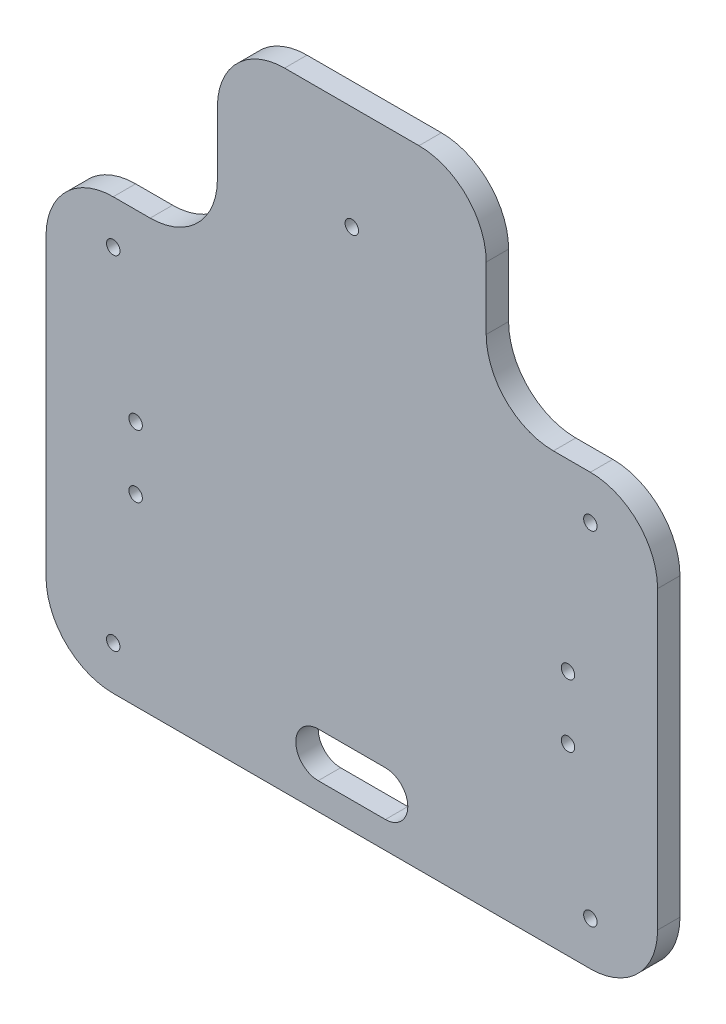
SolidWorks part; units mm, degrees
material "Acrylic (Medium-high impact)"
ref_plane "Front Plane" through (0, 0, 0) normal (0, 0, 1) x (1, 0, 0)
ref_plane "Top Plane" through (0, 0, 0) normal (0, 1, 0) x (1, 0, 0)
ref_plane "Right Plane" through (0, 0, 0) normal (1, 0, 0) x (0, 0, -1)
sketch "Model" plane through (0, 0, 0) normal (0, 0, 1) x (1, 0, 0)
  line L0 (836.1886, 1132.0702) -> (835.7887, 1132.0702)
  line L1 (836.1886, 1132.0702) -> (835.7887, 1132.0702)
  line L2 (836.5018, 1132.0643) -> (836.1886, 1132.0702)
  line L3 (836.5018, 1132.0643) -> (836.1886, 1132.0702)
  line L4 (836.7677, 1132.0446) -> (836.5018, 1132.0643)
  line L5 (836.7677, 1132.0446) -> (836.5018, 1132.0643)
  line L6 (836.9883, 1132.0111) -> (836.7677, 1132.0446)
  line L7 (836.9883, 1132.0111) -> (836.7677, 1132.0446)
  line L8 (837.1636, 1131.9638) -> (836.9883, 1132.0111)
  line L9 (837.1636, 1131.9638) -> (836.9883, 1132.0111)
  line L10 (837.3133, 1131.9008) -> (837.1636, 1131.9638)
  line L11 (837.3133, 1131.9008) -> (837.1636, 1131.9638)
  line L12 (837.4611, 1131.8141) -> (837.3133, 1131.9008)
  line L13 (837.4611, 1131.8141) -> (837.3133, 1131.9008)
  line L14 (837.6029, 1131.7077) -> (837.4611, 1131.8141)
  line L15 (837.6029, 1131.7077) -> (837.4611, 1131.8141)
  line L16 (837.7408, 1131.5777) -> (837.6029, 1131.7077)
  line L17 (837.7408, 1131.5777) -> (837.6029, 1131.7077)
  line L18 (837.8156, 1131.495) -> (837.7408, 1131.5777)
  line L19 (837.8156, 1131.495) -> (837.7408, 1131.5777)
  line L20 (837.9082, 1131.3847) -> (837.8156, 1131.495)
  line L21 (837.9082, 1131.3847) -> (837.8156, 1131.495)
  line L22 (838.0146, 1131.2468) -> (837.9082, 1131.3847)
  line L23 (838.0146, 1131.2468) -> (837.9082, 1131.3847)
  line L24 (838.1367, 1131.0833) -> (838.0146, 1131.2468)
  line L25 (838.1367, 1131.0833) -> (838.0146, 1131.2468)
  line L26 (838.2746, 1130.8903) -> (838.1367, 1131.0833)
  line L27 (838.2746, 1130.8903) -> (838.1367, 1131.0833)
  line L28 (838.4262, 1130.6716) -> (838.2746, 1130.8903)
  line L29 (838.4262, 1130.6716) -> (838.2746, 1130.8903)
  line L30 (838.5956, 1130.4254) -> (838.4262, 1130.6716)
  line L31 (838.5956, 1130.4254) -> (838.4262, 1130.6716)
  line L32 (838.7788, 1130.1516) -> (838.5956, 1130.4254)
  line L33 (838.7788, 1130.1516) -> (838.5956, 1130.4254)
  line L34 (840.1971, 1128.0361) -> (838.7788, 1130.1516)
  line L35 (840.1971, 1128.0361) -> (838.7788, 1130.1516)
  line L36 (842.5963, 1128.0361) -> (840.1971, 1128.0361)
  line L37 (842.5963, 1128.0361) -> (840.1971, 1128.0361)
  line L38 (841.4104, 1129.9369) -> (842.5963, 1128.0361)
  line L39 (841.4104, 1129.9369) -> (842.5963, 1128.0361)
  line L40 (841.2371, 1130.2127) -> (841.4104, 1129.9369)
  line L41 (841.2371, 1130.2127) -> (841.4104, 1129.9369)
  line L42 (841.0716, 1130.4648) -> (841.2371, 1130.2127)
  line L43 (841.0716, 1130.4648) -> (841.2371, 1130.2127)
  line L44 (840.916, 1130.6953) -> (841.0716, 1130.4648)
  line L45 (840.916, 1130.6953) -> (841.0716, 1130.4648)
  line L46 (840.7703, 1130.9041) -> (840.916, 1130.6953)
  line L47 (840.7703, 1130.9041) -> (840.916, 1130.6953)
  line L48 (840.6324, 1131.0892) -> (840.7703, 1130.9041)
  line L49 (840.6324, 1131.0892) -> (840.7703, 1130.9041)
  line L50 (840.5044, 1131.2527) -> (840.6324, 1131.0892)
  line L51 (840.5044, 1131.2527) -> (840.6324, 1131.0892)
  line L52 (840.3862, 1131.3945) -> (840.5044, 1131.2527)
  line L53 (840.3862, 1131.3945) -> (840.5044, 1131.2527)
  line L54 (840.2759, 1131.5147) -> (840.3862, 1131.3945)
  line L55 (840.2759, 1131.5147) -> (840.3862, 1131.3945)
  line L56 (840.0513, 1131.7274) -> (840.2759, 1131.5147)
  line L57 (840.0513, 1131.7274) -> (840.2759, 1131.5147)
  line L58 (839.8011, 1131.9323) -> (840.0513, 1131.7274)
  line L59 (839.8011, 1131.9323) -> (840.0513, 1131.7274)
  line L60 (839.5214, 1132.1273) -> (839.8011, 1131.9323)
  line L61 (839.5214, 1132.1273) -> (839.8011, 1131.9323)
  line L62 (839.2142, 1132.3144) -> (839.5214, 1132.1273)
  line L63 (839.2142, 1132.3144) -> (839.5214, 1132.1273)
  line L64 (839.5195, 1132.3676) -> (839.2142, 1132.3144)
  line L65 (839.5195, 1132.3676) -> (839.2142, 1132.3144)
  line L66 (839.8071, 1132.4365) -> (839.5195, 1132.3676)
  line L67 (839.8071, 1132.4365) -> (839.5195, 1132.3676)
  line L68 (840.0769, 1132.5212) -> (839.8071, 1132.4365)
  line L69 (840.0769, 1132.5212) -> (839.8071, 1132.4365)
  line L70 (840.329, 1132.6237) -> (840.0769, 1132.5212)
  line L71 (840.329, 1132.6237) -> (840.0769, 1132.5212)
  line L72 (840.5634, 1132.7399) -> (840.329, 1132.6237)
  line L73 (840.5634, 1132.7399) -> (840.329, 1132.6237)
  line L74 (840.7782, 1132.8738) -> (840.5634, 1132.7399)
  line L75 (840.7782, 1132.8738) -> (840.5634, 1132.7399)
  line L76 (840.9771, 1133.0235) -> (840.7782, 1132.8738)
  line L77 (840.9771, 1133.0235) -> (840.7782, 1132.8738)
  line L78 (841.1563, 1133.189) -> (840.9771, 1133.0235)
  line L79 (841.1563, 1133.189) -> (840.9771, 1133.0235)
  line L80 (841.3159, 1133.3702) -> (841.1563, 1133.189)
  line L81 (841.3159, 1133.3702) -> (841.1563, 1133.189)
  line L82 (841.4558, 1133.5652) -> (841.3159, 1133.3702)
  line L83 (841.4558, 1133.5652) -> (841.3159, 1133.3702)
  line L84 (841.572, 1133.774) -> (841.4558, 1133.5652)
  line L85 (841.572, 1133.774) -> (841.4558, 1133.5652)
  line L86 (841.6685, 1133.9966) -> (841.572, 1133.774)
  line L87 (841.6685, 1133.9966) -> (841.572, 1133.774)
  line L88 (841.7433, 1134.233) -> (841.6685, 1133.9966)
  line L89 (841.7433, 1134.233) -> (841.6685, 1133.9966)
  line L90 (841.7965, 1134.4831) -> (841.7433, 1134.233)
  line L91 (841.7965, 1134.4831) -> (841.7433, 1134.233)
  line L92 (841.83, 1134.7471) -> (841.7965, 1134.4831)
  line L93 (841.83, 1134.7471) -> (841.7965, 1134.4831)
  line L94 (841.8399, 1135.0248) -> (841.83, 1134.7471)
  line L95 (841.8399, 1135.0248) -> (841.83, 1134.7471)
  line L96 (841.832, 1135.2454) -> (841.8399, 1135.0248)
  line L97 (841.832, 1135.2454) -> (841.8399, 1135.0248)
  line L98 (841.8123, 1135.4601) -> (841.832, 1135.2454)
  line L99 (841.8123, 1135.4601) -> (841.832, 1135.2454)
  line L100 (841.7768, 1135.665) -> (841.8123, 1135.4601)
  line L101 (841.7768, 1135.665) -> (841.8123, 1135.4601)
  line L102 (841.7296, 1135.8639) -> (841.7768, 1135.665)
  line L103 (841.7296, 1135.8639) -> (841.7768, 1135.665)
  line L104 (841.6665, 1136.053) -> (841.7296, 1135.8639)
  line L105 (841.6665, 1136.053) -> (841.7296, 1135.8639)
  line L106 (841.5897, 1136.2343) -> (841.6665, 1136.053)
  line L107 (841.5897, 1136.2343) -> (841.6665, 1136.053)
  line L108 (841.5011, 1136.4076) -> (841.5897, 1136.2343)
  line L109 (841.5011, 1136.4076) -> (841.5897, 1136.2343)
  line L110 (841.3967, 1136.5731) -> (841.5011, 1136.4076)
  line L111 (841.3967, 1136.5731) -> (841.5011, 1136.4076)
  line L112 (841.1603, 1136.8725) -> (841.3967, 1136.5731)
  line L113 (841.1603, 1136.8725) -> (841.3967, 1136.5731)
  line L114 (840.8924, 1137.1226) -> (841.1603, 1136.8725)
  line L115 (840.8924, 1137.1226) -> (841.1603, 1136.8725)
  line L116 (840.593, 1137.3255) -> (840.8924, 1137.1226)
  line L117 (840.593, 1137.3255) -> (840.8924, 1137.1226)
  line L118 (840.264, 1137.4811) -> (840.593, 1137.3255)
  line L119 (840.264, 1137.4811) -> (840.593, 1137.3255)
  line L120 (840.0769, 1137.5422) -> (840.264, 1137.4811)
  line L121 (840.0769, 1137.5422) -> (840.264, 1137.4811)
  line L122 (839.8622, 1137.5954) -> (840.0769, 1137.5422)
  line L123 (839.8622, 1137.5954) -> (840.0769, 1137.5422)
  line L124 (839.618, 1137.6407) -> (839.8622, 1137.5954)
  line L125 (839.618, 1137.6407) -> (839.8622, 1137.5954)
  line L126 (839.3442, 1137.6781) -> (839.618, 1137.6407)
  line L127 (839.3442, 1137.6781) -> (839.618, 1137.6407)
  line L128 (839.0428, 1137.7057) -> (839.3442, 1137.6781)
  line L129 (839.0428, 1137.7057) -> (839.3442, 1137.6781)
  line L130 (838.7119, 1137.7274) -> (839.0428, 1137.7057)
  line L131 (838.7119, 1137.7274) -> (839.0428, 1137.7057)
  line L132 (838.3534, 1137.7392) -> (838.7119, 1137.7274)
  line L133 (838.3534, 1137.7392) -> (838.7119, 1137.7274)
  line L134 (837.9653, 1137.7431) -> (838.3534, 1137.7392)
  line L135 (837.9653, 1137.7431) -> (838.3534, 1137.7392)
  line L136 (833.7717, 1137.7431) -> (837.9653, 1137.7431)
  line L137 (833.7717, 1137.7431) -> (837.9653, 1137.7431)
  line L138 (833.7717, 1128.0361) -> (833.7717, 1137.7431)
  line L139 (833.7717, 1128.0361) -> (833.7717, 1137.7431)
  line L140 (835.7887, 1128.0361) -> (833.7717, 1128.0361)
  line L141 (835.7887, 1128.0361) -> (833.7717, 1128.0361)
  line L142 (835.7887, 1132.0702) -> (835.7887, 1128.0361)
  line L143 (835.7887, 1132.0702) -> (835.7887, 1128.0361)
  line L144 (851.3546, 1130.1792) -> (847.4801, 1130.1792)
  line L145 (851.3546, 1130.1792) -> (847.4801, 1130.1792)
  line L146 (852.1406, 1128.0361) -> (851.3546, 1130.1792)
  line L147 (852.1406, 1128.0361) -> (851.3546, 1130.1792)
  line L148 (854.396, 1128.0361) -> (852.1406, 1128.0361)
  line L149 (854.396, 1128.0361) -> (852.1406, 1128.0361)
  line L150 (850.6948, 1137.7431) -> (854.396, 1128.0361)
  line L151 (850.6948, 1137.7431) -> (854.396, 1128.0361)
  line L152 (848.138, 1137.7431) -> (850.6948, 1137.7431)
  line L153 (848.138, 1137.7431) -> (850.6948, 1137.7431)
  line L154 (844.4368, 1128.0361) -> (848.138, 1137.7431)
  line L155 (844.4368, 1128.0361) -> (848.138, 1137.7431)
  line L156 (846.6922, 1128.0361) -> (844.4368, 1128.0361)
  line L157 (846.6922, 1128.0361) -> (844.4368, 1128.0361)
  line L158 (847.4801, 1130.1792) -> (846.6922, 1128.0361)
  line L159 (847.4801, 1130.1792) -> (846.6922, 1128.0361)
  line L160 (850.4446, 1044.1431) -> (850.4446, 1039.1431)
  line L161 (850.4446, 1044.1431) -> (850.4446, 1039.1431)
  line L162 (825.4446, 1044.1431) -> (850.4446, 1044.1431)
  line L163 (825.4446, 1044.1431) -> (850.4446, 1044.1431)
  line L164 (825.4446, 1039.1431) -> (825.4446, 1044.1431)
  line L165 (825.4446, 1039.1431) -> (825.4446, 1044.1431)
  line L166 (850.4446, 1039.1431) -> (825.4446, 1039.1431)
  line L167 (850.4446, 1039.1431) -> (825.4446, 1039.1431)
  line L168 (822.752, 1129.8246) -> (822.6141, 1130.1575)
  line L169 (822.752, 1129.8246) -> (822.6141, 1130.1575)
  line L170 (822.9155, 1129.5193) -> (822.752, 1129.8246)
  line L171 (822.9155, 1129.5193) -> (822.752, 1129.8246)
  line L172 (823.1026, 1129.2396) -> (822.9155, 1129.5193)
  line L173 (823.1026, 1129.2396) -> (822.9155, 1129.5193)
  line L174 (823.3153, 1128.9875) -> (823.1026, 1129.2396)
  line L175 (823.3153, 1128.9875) -> (823.1026, 1129.2396)
  line L176 (823.5537, 1128.761) -> (823.3153, 1128.9875)
  line L177 (823.5537, 1128.761) -> (823.3153, 1128.9875)
  line L178 (823.8157, 1128.562) -> (823.5537, 1128.761)
  line L179 (823.8157, 1128.562) -> (823.5537, 1128.761)
  line L180 (824.1033, 1128.3887) -> (823.8157, 1128.562)
  line L181 (824.1033, 1128.3887) -> (823.8157, 1128.562)
  line L182 (824.4145, 1128.2429) -> (824.1033, 1128.3887)
  line L183 (824.4145, 1128.2429) -> (824.1033, 1128.3887)
  line L184 (824.7513, 1128.1227) -> (824.4145, 1128.2429)
  line L185 (824.7513, 1128.1227) -> (824.4145, 1128.2429)
  line L186 (825.1137, 1128.0302) -> (824.7513, 1128.1227)
  line L187 (825.1137, 1128.0302) -> (824.7513, 1128.1227)
  line L188 (825.4998, 1127.9632) -> (825.1137, 1128.0302)
  line L189 (825.4998, 1127.9632) -> (825.1137, 1128.0302)
  line L190 (825.9115, 1127.9238) -> (825.4998, 1127.9632)
  line L191 (825.9115, 1127.9238) -> (825.4998, 1127.9632)
  line L192 (826.3488, 1127.91) -> (825.9115, 1127.9238)
  line L193 (826.3488, 1127.91) -> (825.9115, 1127.9238)
  line L194 (826.8393, 1127.9238) -> (826.3488, 1127.91)
  line L195 (826.8393, 1127.9238) -> (826.3488, 1127.91)
  line L196 (827.2982, 1127.9632) -> (826.8393, 1127.9238)
  line L197 (827.2982, 1127.9632) -> (826.8393, 1127.9238)
  line L198 (827.7217, 1128.0282) -> (827.2982, 1127.9632)
  line L199 (827.7217, 1128.0282) -> (827.2982, 1127.9632)
  line L200 (828.1117, 1128.1208) -> (827.7217, 1128.0282)
  line L201 (828.1117, 1128.1208) -> (827.7217, 1128.0282)
  line L202 (828.4683, 1128.239) -> (828.1117, 1128.1208)
  line L203 (828.4683, 1128.239) -> (828.1117, 1128.1208)
  line L204 (828.7913, 1128.3847) -> (828.4683, 1128.239)
  line L205 (828.7913, 1128.3847) -> (828.4683, 1128.239)
  line L206 (829.0809, 1128.5561) -> (828.7913, 1128.3847)
  line L207 (829.0809, 1128.5561) -> (828.7913, 1128.3847)
  line L208 (829.3369, 1128.7531) -> (829.0809, 1128.5561)
  line L209 (829.3369, 1128.7531) -> (829.0809, 1128.5561)
  line L210 (829.5615, 1128.9698) -> (829.3369, 1128.7531)
  line L211 (829.5615, 1128.9698) -> (829.3369, 1128.7531)
  line L212 (829.7545, 1129.2002) -> (829.5615, 1128.9698)
  line L213 (829.7545, 1129.2002) -> (829.5615, 1128.9698)
  line L214 (829.92, 1129.4425) -> (829.7545, 1129.2002)
  line L215 (829.92, 1129.4425) -> (829.7545, 1129.2002)
  line L216 (830.0539, 1129.6966) -> (829.92, 1129.4425)
  line L217 (830.0539, 1129.6966) -> (829.92, 1129.4425)
  line L218 (830.1583, 1129.9625) -> (830.0539, 1129.6966)
  line L219 (830.1583, 1129.9625) -> (830.0539, 1129.6966)
  line L220 (830.2332, 1130.2422) -> (830.1583, 1129.9625)
  line L221 (830.2332, 1130.2422) -> (830.1583, 1129.9625)
  line L222 (830.2765, 1130.5337) -> (830.2332, 1130.2422)
  line L223 (830.2765, 1130.5337) -> (830.2332, 1130.2422)
  line L224 (830.2923, 1130.8371) -> (830.2765, 1130.5337)
  line L225 (830.2923, 1130.8371) -> (830.2765, 1130.5337)
  line L226 (830.2706, 1131.2488) -> (830.2923, 1130.8371)
  line L227 (830.2706, 1131.2488) -> (830.2923, 1130.8371)
  line L228 (830.2036, 1131.6289) -> (830.2706, 1131.2488)
  line L229 (830.2036, 1131.6289) -> (830.2706, 1131.2488)
  line L230 (830.0914, 1131.9776) -> (830.2036, 1131.6289)
  line L231 (830.0914, 1131.9776) -> (830.2036, 1131.6289)
  line L232 (829.9338, 1132.2928) -> (830.0914, 1131.9776)
  line L233 (829.9338, 1132.2928) -> (830.0914, 1131.9776)
  line L234 (829.7348, 1132.5803) -> (829.9338, 1132.2928)
  line L235 (829.7348, 1132.5803) -> (829.9338, 1132.2928)
  line L236 (829.4965, 1132.8384) -> (829.7348, 1132.5803)
  line L237 (829.4965, 1132.8384) -> (829.7348, 1132.5803)
  line L238 (829.2187, 1133.0708) -> (829.4965, 1132.8384)
  line L239 (829.2187, 1133.0708) -> (829.4965, 1132.8384)
  line L240 (828.8996, 1133.2737) -> (829.2187, 1133.0708)
  line L241 (828.8996, 1133.2737) -> (829.2187, 1133.0708)
  line L242 (828.7184, 1133.3682) -> (828.8996, 1133.2737)
  line L243 (828.7184, 1133.3682) -> (828.8996, 1133.2737)
  line L244 (828.5096, 1133.4628) -> (828.7184, 1133.3682)
  line L245 (828.5096, 1133.4628) -> (828.7184, 1133.3682)
  line L246 (828.2772, 1133.5554) -> (828.5096, 1133.4628)
  line L247 (828.2772, 1133.5554) -> (828.5096, 1133.4628)
  line L248 (828.0172, 1133.6499) -> (828.2772, 1133.5554)
  line L249 (828.0172, 1133.6499) -> (828.2772, 1133.5554)
  line L250 (827.7316, 1133.7405) -> (828.0172, 1133.6499)
  line L251 (827.7316, 1133.7405) -> (828.0172, 1133.6499)
  line L252 (827.4203, 1133.8331) -> (827.7316, 1133.7405)
  line L253 (827.4203, 1133.8331) -> (827.7316, 1133.7405)
  line L254 (827.0835, 1133.9237) -> (827.4203, 1133.8331)
  line L255 (827.0835, 1133.9237) -> (827.4203, 1133.8331)
  line L256 (826.7211, 1134.0143) -> (827.0835, 1133.9237)
  line L257 (826.7211, 1134.0143) -> (827.0835, 1133.9237)
  line L258 (826.3823, 1134.0971) -> (826.7211, 1134.0143)
  line L259 (826.3823, 1134.0971) -> (826.7211, 1134.0143)
  line L260 (826.073, 1134.1778) -> (826.3823, 1134.0971)
  line L261 (826.073, 1134.1778) -> (826.3823, 1134.0971)
  line L262 (825.7973, 1134.2566) -> (826.073, 1134.1778)
  line L263 (825.7973, 1134.2566) -> (826.073, 1134.1778)
  line L264 (825.555, 1134.3334) -> (825.7973, 1134.2566)
  line L265 (825.555, 1134.3334) -> (825.7973, 1134.2566)
  line L266 (825.3422, 1134.4083) -> (825.555, 1134.3334)
  line L267 (825.3422, 1134.4083) -> (825.555, 1134.3334)
  line L268 (825.161, 1134.4792) -> (825.3422, 1134.4083)
  line L269 (825.161, 1134.4792) -> (825.3422, 1134.4083)
  line L270 (825.0133, 1134.5501) -> (825.161, 1134.4792)
  line L271 (825.0133, 1134.5501) -> (825.161, 1134.4792)
  line L272 (824.8971, 1134.6191) -> (825.0133, 1134.5501)
  line L273 (824.8971, 1134.6191) -> (825.0133, 1134.5501)
  line L274 (824.7198, 1134.7628) -> (824.8971, 1134.6191)
  line L275 (824.7198, 1134.7628) -> (824.8971, 1134.6191)
  line L276 (824.5937, 1134.9224) -> (824.7198, 1134.7628)
  line L277 (824.5937, 1134.9224) -> (824.7198, 1134.7628)
  line L278 (824.5189, 1135.0957) -> (824.5937, 1134.9224)
  line L279 (824.5189, 1135.0957) -> (824.5937, 1134.9224)
  line L280 (824.4933, 1135.2868) -> (824.5189, 1135.0957)
  line L281 (824.4933, 1135.2868) -> (824.5189, 1135.0957)
  line L282 (824.5011, 1135.3853) -> (824.4933, 1135.2868)
  line L283 (824.5011, 1135.3853) -> (824.4933, 1135.2868)
  line L284 (824.5228, 1135.4798) -> (824.5011, 1135.3853)
  line L285 (824.5228, 1135.4798) -> (824.5011, 1135.3853)
  line L286 (824.5583, 1135.5705) -> (824.5228, 1135.4798)
  line L287 (824.5583, 1135.5705) -> (824.5228, 1135.4798)
  line L288 (824.6075, 1135.6552) -> (824.5583, 1135.5705)
  line L289 (824.6075, 1135.6552) -> (824.5583, 1135.5705)
  line L290 (824.6725, 1135.7379) -> (824.6075, 1135.6552)
  line L291 (824.6725, 1135.7379) -> (824.6075, 1135.6552)
  line L292 (824.7513, 1135.8147) -> (824.6725, 1135.7379)
  line L293 (824.7513, 1135.8147) -> (824.6725, 1135.7379)
  line L294 (824.8439, 1135.8896) -> (824.7513, 1135.8147)
  line L295 (824.8439, 1135.8896) -> (824.7513, 1135.8147)
  line L296 (824.9503, 1135.9585) -> (824.8439, 1135.8896)
  line L297 (824.9503, 1135.9585) -> (824.8439, 1135.8896)
  line L298 (825.0704, 1136.0215) -> (824.9503, 1135.9585)
  line L299 (825.0704, 1136.0215) -> (824.9503, 1135.9585)
  line L300 (825.2024, 1136.0767) -> (825.0704, 1136.0215)
  line L301 (825.2024, 1136.0767) -> (825.0704, 1136.0215)
  line L302 (825.3481, 1136.124) -> (825.2024, 1136.0767)
  line L303 (825.3481, 1136.124) -> (825.2024, 1136.0767)
  line L304 (825.5038, 1136.1634) -> (825.3481, 1136.124)
  line L305 (825.5038, 1136.1634) -> (825.3481, 1136.124)
  line L306 (825.6732, 1136.1929) -> (825.5038, 1136.1634)
  line L307 (825.6732, 1136.1929) -> (825.5038, 1136.1634)
  line L308 (825.8544, 1136.2126) -> (825.6732, 1136.1929)
  line L309 (825.8544, 1136.2126) -> (825.6732, 1136.1929)
  line L310 (826.0474, 1136.2264) -> (825.8544, 1136.2126)
  line L311 (826.0474, 1136.2264) -> (825.8544, 1136.2126)
  line L312 (826.2523, 1136.2303) -> (826.0474, 1136.2264)
  line L313 (826.2523, 1136.2303) -> (826.0474, 1136.2264)
  line L314 (826.4571, 1136.2264) -> (826.2523, 1136.2303)
  line L315 (826.4571, 1136.2264) -> (826.2523, 1136.2303)
  line L316 (826.6502, 1136.2106) -> (826.4571, 1136.2264)
  line L317 (826.6502, 1136.2106) -> (826.4571, 1136.2264)
  line L318 (826.8314, 1136.187) -> (826.6502, 1136.2106)
  line L319 (826.8314, 1136.187) -> (826.6502, 1136.2106)
  line L320 (827.0008, 1136.1535) -> (826.8314, 1136.187)
  line L321 (827.0008, 1136.1535) -> (826.8314, 1136.187)
  line L322 (827.1564, 1136.1102) -> (827.0008, 1136.1535)
  line L323 (827.1564, 1136.1102) -> (827.0008, 1136.1535)
  line L324 (827.3022, 1136.057) -> (827.1564, 1136.1102)
  line L325 (827.3022, 1136.057) -> (827.1564, 1136.1102)
  line L326 (827.4341, 1135.9959) -> (827.3022, 1136.057)
  line L327 (827.4341, 1135.9959) -> (827.3022, 1136.057)
  line L328 (827.5543, 1135.923) -> (827.4341, 1135.9959)
  line L329 (827.5543, 1135.923) -> (827.4341, 1135.9959)
  line L330 (827.6626, 1135.8383) -> (827.5543, 1135.923)
  line L331 (827.6626, 1135.8383) -> (827.5543, 1135.923)
  line L332 (827.7631, 1135.7399) -> (827.6626, 1135.8383)
  line L333 (827.7631, 1135.7399) -> (827.6626, 1135.8383)
  line L334 (827.8517, 1135.6276) -> (827.7631, 1135.7399)
  line L335 (827.8517, 1135.6276) -> (827.7631, 1135.7399)
  line L336 (827.9325, 1135.4995) -> (827.8517, 1135.6276)
  line L337 (827.9325, 1135.4995) -> (827.8517, 1135.6276)
  line L338 (828.0014, 1135.3577) -> (827.9325, 1135.4995)
  line L339 (828.0014, 1135.3577) -> (827.9325, 1135.4995)
  line L340 (828.0605, 1135.2001) -> (828.0014, 1135.3577)
  line L341 (828.0605, 1135.2001) -> (828.0014, 1135.3577)
  line L342 (828.1098, 1135.0288) -> (828.0605, 1135.2001)
  line L343 (828.1098, 1135.0288) -> (828.0605, 1135.2001)
  line L344 (828.1492, 1134.8436) -> (828.1098, 1135.0288)
  line L345 (828.1492, 1134.8436) -> (828.1098, 1135.0288)
  line L346 (830.0401, 1134.9697) -> (828.1492, 1134.8436)
  line L347 (830.0401, 1134.9697) -> (828.1492, 1134.8436)
  line L348 (830.0106, 1135.3085) -> (830.0401, 1134.9697)
  line L349 (830.0106, 1135.3085) -> (830.0401, 1134.9697)
  line L350 (829.9535, 1135.6276) -> (830.0106, 1135.3085)
  line L351 (829.9535, 1135.6276) -> (830.0106, 1135.3085)
  line L352 (829.8668, 1135.927) -> (829.9535, 1135.6276)
  line L353 (829.8668, 1135.927) -> (829.9535, 1135.6276)
  line L354 (829.7506, 1136.2047) -> (829.8668, 1135.927)
  line L355 (829.7506, 1136.2047) -> (829.8668, 1135.927)
  line L356 (829.6068, 1136.4628) -> (829.7506, 1136.2047)
  line L357 (829.6068, 1136.4628) -> (829.7506, 1136.2047)
  line L358 (829.4335, 1136.7011) -> (829.6068, 1136.4628)
  line L359 (829.4335, 1136.7011) -> (829.6068, 1136.4628)
  line L360 (829.2306, 1136.9197) -> (829.4335, 1136.7011)
  line L361 (829.2306, 1136.9197) -> (829.4335, 1136.7011)
  line L362 (828.9981, 1137.1167) -> (829.2306, 1136.9197)
  line L363 (828.9981, 1137.1167) -> (829.2306, 1136.9197)
  line L364 (828.7401, 1137.294) -> (828.9981, 1137.1167)
  line L365 (828.7401, 1137.294) -> (828.9981, 1137.1167)
  line L366 (828.4584, 1137.4457) -> (828.7401, 1137.294)
  line L367 (828.4584, 1137.4457) -> (828.7401, 1137.294)
  line L368 (828.1511, 1137.5757) -> (828.4584, 1137.4457)
  line L369 (828.1511, 1137.5757) -> (828.4584, 1137.4457)
  line L370 (827.8202, 1137.682) -> (828.1511, 1137.5757)
  line L371 (827.8202, 1137.682) -> (828.1511, 1137.5757)
  line L372 (827.4657, 1137.7628) -> (827.8202, 1137.682)
  line L373 (827.4657, 1137.7628) -> (827.8202, 1137.682)
  line L374 (827.0875, 1137.8219) -> (827.4657, 1137.7628)
  line L375 (827.0875, 1137.8219) -> (827.4657, 1137.7628)
  line L376 (826.6856, 1137.8574) -> (827.0875, 1137.8219)
  line L377 (826.6856, 1137.8574) -> (827.0875, 1137.8219)
  line L378 (826.2582, 1137.8692) -> (826.6856, 1137.8574)
  line L379 (826.2582, 1137.8692) -> (826.6856, 1137.8574)
  line L380 (825.9726, 1137.8633) -> (826.2582, 1137.8692)
  line L381 (825.9726, 1137.8633) -> (826.2582, 1137.8692)
  line L382 (825.6988, 1137.8495) -> (825.9726, 1137.8633)
  line L383 (825.6988, 1137.8495) -> (825.9726, 1137.8633)
  line L384 (825.4368, 1137.8239) -> (825.6988, 1137.8495)
  line L385 (825.4368, 1137.8239) -> (825.6988, 1137.8495)
  line L386 (825.1847, 1137.7884) -> (825.4368, 1137.8239)
  line L387 (825.1847, 1137.7884) -> (825.4368, 1137.8239)
  line L388 (824.9463, 1137.7431) -> (825.1847, 1137.7884)
  line L389 (824.9463, 1137.7431) -> (825.1847, 1137.7884)
  line L390 (824.7178, 1137.688) -> (824.9463, 1137.7431)
  line L391 (824.7178, 1137.688) -> (824.9463, 1137.7431)
  line L392 (824.5031, 1137.623) -> (824.7178, 1137.688)
  line L393 (824.5031, 1137.623) -> (824.7178, 1137.688)
  line L394 (824.2983, 1137.5481) -> (824.5031, 1137.623)
  line L395 (824.2983, 1137.5481) -> (824.5031, 1137.623)
  line L396 (823.922, 1137.3689) -> (824.2983, 1137.5481)
  line L397 (823.922, 1137.3689) -> (824.2983, 1137.5481)
  line L398 (823.5911, 1137.1522) -> (823.922, 1137.3689)
  line L399 (823.5911, 1137.1522) -> (823.922, 1137.3689)
  line L400 (823.2996, 1136.8961) -> (823.5911, 1137.1522)
  line L401 (823.2996, 1136.8961) -> (823.5911, 1137.1522)
  line L402 (823.0534, 1136.6006) -> (823.2996, 1136.8961)
  line L403 (823.0534, 1136.6006) -> (823.2996, 1136.8961)
  line L404 (822.947, 1136.4411) -> (823.0534, 1136.6006)
  line L405 (822.947, 1136.4411) -> (823.0534, 1136.6006)
  line L406 (822.8564, 1136.2776) -> (822.947, 1136.4411)
  line L407 (822.8564, 1136.2776) -> (822.947, 1136.4411)
  line L408 (822.7776, 1136.1082) -> (822.8564, 1136.2776)
  line L409 (822.7776, 1136.1082) -> (822.8564, 1136.2776)
  line L410 (822.7146, 1135.9329) -> (822.7776, 1136.1082)
  line L411 (822.7146, 1135.9329) -> (822.7776, 1136.1082)
  line L412 (822.6653, 1135.7536) -> (822.7146, 1135.9329)
  line L413 (822.6653, 1135.7536) -> (822.7146, 1135.9329)
  line L414 (822.6299, 1135.5705) -> (822.6653, 1135.7536)
  line L415 (822.6299, 1135.5705) -> (822.6653, 1135.7536)
  line L416 (822.6102, 1135.3814) -> (822.6299, 1135.5705)
  line L417 (822.6102, 1135.3814) -> (822.6299, 1135.5705)
  line L418 (822.6023, 1135.1883) -> (822.6102, 1135.3814)
  line L419 (822.6023, 1135.1883) -> (822.6102, 1135.3814)
  line L420 (822.624, 1134.8574) -> (822.6023, 1135.1883)
  line L421 (822.624, 1134.8574) -> (822.6023, 1135.1883)
  line L422 (822.6909, 1134.5363) -> (822.624, 1134.8574)
  line L423 (822.6909, 1134.5363) -> (822.624, 1134.8574)
  line L424 (822.7993, 1134.2271) -> (822.6909, 1134.5363)
  line L425 (822.7993, 1134.2271) -> (822.6909, 1134.5363)
  line L426 (822.9529, 1133.9277) -> (822.7993, 1134.2271)
  line L427 (822.9529, 1133.9277) -> (822.7993, 1134.2271)
  line L428 (823.144, 1133.6499) -> (822.9529, 1133.9277)
  line L429 (823.144, 1133.6499) -> (822.9529, 1133.9277)
  line L430 (823.3646, 1133.3998) -> (823.144, 1133.6499)
  line L431 (823.3646, 1133.3998) -> (823.144, 1133.6499)
  line L432 (823.6148, 1133.1772) -> (823.3646, 1133.3998)
  line L433 (823.6148, 1133.1772) -> (823.3646, 1133.3998)
  line L434 (823.8964, 1132.9822) -> (823.6148, 1133.1772)
  line L435 (823.8964, 1132.9822) -> (823.6148, 1133.1772)
  line L436 (824.056, 1132.8935) -> (823.8964, 1132.9822)
  line L437 (824.056, 1132.8935) -> (823.8964, 1132.9822)
  line L438 (824.2352, 1132.8069) -> (824.056, 1132.8935)
  line L439 (824.2352, 1132.8069) -> (824.056, 1132.8935)
  line L440 (824.4381, 1132.7202) -> (824.2352, 1132.8069)
  line L441 (824.4381, 1132.7202) -> (824.2352, 1132.8069)
  line L442 (824.6607, 1132.6375) -> (824.4381, 1132.7202)
  line L443 (824.6607, 1132.6375) -> (824.4381, 1132.7202)
  line L444 (824.905, 1132.5547) -> (824.6607, 1132.6375)
  line L445 (824.905, 1132.5547) -> (824.6607, 1132.6375)
  line L446 (825.1709, 1132.4759) -> (824.905, 1132.5547)
  line L447 (825.1709, 1132.4759) -> (824.905, 1132.5547)
  line L448 (825.4585, 1132.3972) -> (825.1709, 1132.4759)
  line L449 (825.4585, 1132.3972) -> (825.1709, 1132.4759)
  line L450 (825.7677, 1132.3203) -> (825.4585, 1132.3972)
  line L451 (825.7677, 1132.3203) -> (825.4585, 1132.3972)
  line L452 (826.1085, 1132.2376) -> (825.7677, 1132.3203)
  line L453 (826.1085, 1132.2376) -> (825.7677, 1132.3203)
  line L454 (826.4177, 1132.1627) -> (826.1085, 1132.2376)
  line L455 (826.4177, 1132.1627) -> (826.1085, 1132.2376)
  line L456 (826.6935, 1132.0918) -> (826.4177, 1132.1627)
  line L457 (826.6935, 1132.0918) -> (826.4177, 1132.1627)
  line L458 (826.9397, 1132.0268) -> (826.6935, 1132.0918)
  line L459 (826.9397, 1132.0268) -> (826.6935, 1132.0918)
  line L460 (827.1525, 1131.9697) -> (826.9397, 1132.0268)
  line L461 (827.1525, 1131.9697) -> (826.9397, 1132.0268)
  line L462 (827.3337, 1131.9165) -> (827.1525, 1131.9697)
  line L463 (827.3337, 1131.9165) -> (827.1525, 1131.9697)
  line L464 (827.4814, 1131.8712) -> (827.3337, 1131.9165)
  line L465 (827.4814, 1131.8712) -> (827.3337, 1131.9165)
  line L466 (827.5996, 1131.8299) -> (827.4814, 1131.8712)
  line L467 (827.5996, 1131.8299) -> (827.4814, 1131.8712)
  line L468 (827.7887, 1131.7491) -> (827.5996, 1131.8299)
  line L469 (827.7887, 1131.7491) -> (827.5996, 1131.8299)
  line L470 (827.9542, 1131.6585) -> (827.7887, 1131.7491)
  line L471 (827.9542, 1131.6585) -> (827.7887, 1131.7491)
  line L472 (828.0901, 1131.558) -> (827.9542, 1131.6585)
  line L473 (828.0901, 1131.558) -> (827.9542, 1131.6585)
  line L474 (828.2023, 1131.4458) -> (828.0901, 1131.558)
  line L475 (828.2023, 1131.4458) -> (828.0901, 1131.558)
  line L476 (828.289, 1131.3236) -> (828.2023, 1131.4458)
  line L477 (828.289, 1131.3236) -> (828.2023, 1131.4458)
  line L478 (828.352, 1131.1877) -> (828.289, 1131.3236)
  line L479 (828.352, 1131.1877) -> (828.289, 1131.3236)
  line L480 (828.3895, 1131.04) -> (828.352, 1131.1877)
  line L481 (828.3895, 1131.04) -> (828.352, 1131.1877)
  line L482 (828.4013, 1130.8804) -> (828.3895, 1131.04)
  line L483 (828.4013, 1130.8804) -> (828.3895, 1131.04)
  line L484 (828.3934, 1130.7425) -> (828.4013, 1130.8804)
  line L485 (828.3934, 1130.7425) -> (828.4013, 1130.8804)
  line L486 (828.3678, 1130.6086) -> (828.3934, 1130.7425)
  line L487 (828.3678, 1130.6086) -> (828.3934, 1130.7425)
  line L488 (828.3264, 1130.4825) -> (828.3678, 1130.6086)
  line L489 (828.3264, 1130.4825) -> (828.3678, 1130.6086)
  line L490 (828.2693, 1130.3604) -> (828.3264, 1130.4825)
  line L491 (828.2693, 1130.3604) -> (828.3264, 1130.4825)
  line L492 (828.1964, 1130.2442) -> (828.2693, 1130.3604)
  line L493 (828.1964, 1130.2442) -> (828.2693, 1130.3604)
  line L494 (828.1058, 1130.1339) -> (828.1964, 1130.2442)
  line L495 (828.1058, 1130.1339) -> (828.1964, 1130.2442)
  line L496 (827.9995, 1130.0295) -> (828.1058, 1130.1339)
  line L497 (827.9995, 1130.0295) -> (828.1058, 1130.1339)
  line L498 (827.8754, 1129.931) -> (827.9995, 1130.0295)
  line L499 (827.8754, 1129.931) -> (827.9995, 1130.0295)
  line L500 (827.7375, 1129.8424) -> (827.8754, 1129.931)
  line L501 (827.7375, 1129.8424) -> (827.8754, 1129.931)
  line L502 (827.5878, 1129.7636) -> (827.7375, 1129.8424)
  line L503 (827.5878, 1129.7636) -> (827.7375, 1129.8424)
  line L504 (827.4263, 1129.6986) -> (827.5878, 1129.7636)
  line L505 (827.4263, 1129.6986) -> (827.5878, 1129.7636)
  line L506 (827.2509, 1129.6454) -> (827.4263, 1129.6986)
  line L507 (827.2509, 1129.6454) -> (827.4263, 1129.6986)
  line L508 (827.0638, 1129.602) -> (827.2509, 1129.6454)
  line L509 (827.0638, 1129.602) -> (827.2509, 1129.6454)
  line L510 (826.8649, 1129.5725) -> (827.0638, 1129.602)
  line L511 (826.8649, 1129.5725) -> (827.0638, 1129.602)
  line L512 (826.6541, 1129.5548) -> (826.8649, 1129.5725)
  line L513 (826.6541, 1129.5548) -> (826.8649, 1129.5725)
  line L514 (826.4296, 1129.5489) -> (826.6541, 1129.5548)
  line L515 (826.4296, 1129.5489) -> (826.6541, 1129.5548)
  line L516 (826.203, 1129.5567) -> (826.4296, 1129.5489)
  line L517 (826.203, 1129.5567) -> (826.4296, 1129.5489)
  line L518 (825.9903, 1129.5784) -> (826.203, 1129.5567)
  line L519 (825.9903, 1129.5784) -> (826.203, 1129.5567)
  line L520 (825.7874, 1129.6158) -> (825.9903, 1129.5784)
  line L521 (825.7874, 1129.6158) -> (825.9903, 1129.5784)
  line L522 (825.5983, 1129.667) -> (825.7874, 1129.6158)
  line L523 (825.5983, 1129.667) -> (825.7874, 1129.6158)
  line L524 (825.4191, 1129.734) -> (825.5983, 1129.667)
  line L525 (825.4191, 1129.734) -> (825.5983, 1129.667)
  line L526 (825.2536, 1129.8148) -> (825.4191, 1129.734)
  line L527 (825.2536, 1129.8148) -> (825.4191, 1129.734)
  line L528 (825.098, 1129.9113) -> (825.2536, 1129.8148)
  line L529 (825.098, 1129.9113) -> (825.2536, 1129.8148)
  line L530 (824.9562, 1130.0216) -> (825.098, 1129.9113)
  line L531 (824.9562, 1130.0216) -> (825.098, 1129.9113)
  line L532 (824.8242, 1130.1477) -> (824.9562, 1130.0216)
  line L533 (824.8242, 1130.1477) -> (824.9562, 1130.0216)
  line L534 (824.706, 1130.2875) -> (824.8242, 1130.1477)
  line L535 (824.706, 1130.2875) -> (824.8242, 1130.1477)
  line L536 (824.5996, 1130.4431) -> (824.706, 1130.2875)
  line L537 (824.5996, 1130.4431) -> (824.706, 1130.2875)
  line L538 (824.5031, 1130.6125) -> (824.5996, 1130.4431)
  line L539 (824.5031, 1130.6125) -> (824.5996, 1130.4431)
  line L540 (824.4204, 1130.7977) -> (824.5031, 1130.6125)
  line L541 (824.4204, 1130.7977) -> (824.5031, 1130.6125)
  line L542 (824.3495, 1130.9966) -> (824.4204, 1130.7977)
  line L543 (824.3495, 1130.9966) -> (824.4204, 1130.7977)
  line L544 (824.2884, 1131.2113) -> (824.3495, 1130.9966)
  line L545 (824.2884, 1131.2113) -> (824.3495, 1130.9966)
  line L546 (824.2411, 1131.4398) -> (824.2884, 1131.2113)
  line L547 (824.2411, 1131.4398) -> (824.2884, 1131.2113)
  line L548 (822.3502, 1131.3138) -> (824.2411, 1131.4398)
  line L549 (822.3502, 1131.3138) -> (824.2411, 1131.4398)
  line L550 (822.4132, 1130.9021) -> (822.3502, 1131.3138)
  line L551 (822.4132, 1130.9021) -> (822.3502, 1131.3138)
  line L552 (822.5018, 1130.516) -> (822.4132, 1130.9021)
  line L553 (822.5018, 1130.516) -> (822.4132, 1130.9021)
  line L554 (822.6141, 1130.1575) -> (822.5018, 1130.516)
  line L555 (822.6141, 1130.1575) -> (822.5018, 1130.516)
  line L556 (845.4446, 1019.1431) -> (830.4446, 1019.1431)
  line L557 (830.4446, 1019.1431) -> (845.4446, 1019.1431)
  line L558 (845.4446, 1009.1431) -> (830.4446, 1009.1431)
  line L559 (845.4446, 1009.1431) -> (830.4446, 1009.1431)
  line L560 (769.6946, 1084.1431) -> (769.6946, 1018.1431)
  line L561 (769.6946, 1084.1431) -> (769.6946, 1018.1431)
  line L562 (784.6946, 1099.1431) -> (792.9446, 1099.1431)
  line L563 (792.9446, 1099.1431) -> (784.6946, 1099.1431)
  line L564 (807.9446, 1128.1431) -> (807.9446, 1114.1431)
  line L565 (807.9446, 1128.1431) -> (807.9446, 1114.1431)
  line L566 (822.9446, 1143.1431) -> (852.9446, 1143.1431)
  line L567 (852.9446, 1143.1431) -> (822.9446, 1143.1431)
  line L568 (867.9446, 1128.1431) -> (867.9446, 1114.1431)
  line L569 (867.9446, 1114.1431) -> (867.9446, 1128.1431)
  line L570 (891.1946, 1099.1431) -> (882.9446, 1099.1431)
  line L571 (891.1946, 1099.1431) -> (882.9446, 1099.1431)
  line L572 (906.1946, 1084.1431) -> (906.1946, 1018.1431)
  line L573 (906.1946, 1018.1431) -> (906.1946, 1084.1431)
  line L574 (891.1946, 1003.1431) -> (784.6946, 1003.1431)
  line L575 (784.6946, 1003.1431) -> (891.1946, 1003.1431)
  line L576 (891.1946, 1099.1431) -> (882.9446, 1099.1431)
  line L577 (826.6541, 1129.5548) -> (826.8649, 1129.5725)
  line L578 (825.098, 1129.9113) -> (825.2536, 1129.8148)
  line L579 (824.2884, 1131.2113) -> (824.3495, 1130.9966)
  line L580 (824.2411, 1131.4398) -> (824.2884, 1131.2113)
  line L581 (891.1946, 1003.1431) -> (784.6946, 1003.1431)
  line L582 (845.4446, 1009.1431) -> (830.4446, 1009.1431)
  line L583 (826.203, 1129.5567) -> (826.4296, 1129.5489)
  line L584 (826.4296, 1129.5489) -> (826.6541, 1129.5548)
  line L585 (825.9903, 1129.5784) -> (826.203, 1129.5567)
  line L586 (824.4204, 1130.7977) -> (824.5031, 1130.6125)
  line L587 (825.4191, 1129.734) -> (825.5983, 1129.667)
  line L588 (826.8649, 1129.5725) -> (827.0638, 1129.602)
  line L589 (824.8242, 1130.1477) -> (824.9562, 1130.0216)
  line L590 (845.4446, 1019.1431) -> (830.4446, 1019.1431)
  line L591 (784.6946, 1099.1431) -> (792.9446, 1099.1431)
  line L592 (827.7887, 1131.7491) -> (827.5996, 1131.8299)
  line L593 (826.4177, 1132.1627) -> (826.1085, 1132.2376)
  line L594 (822.6023, 1135.1883) -> (822.6102, 1135.3814)
  line L595 (823.3646, 1133.3998) -> (823.144, 1133.6499)
  line L596 (824.056, 1132.8935) -> (823.8964, 1132.9822)
  line L597 (828.289, 1131.3236) -> (828.2023, 1131.4458)
  line L598 (825.7677, 1132.3203) -> (825.4585, 1132.3972)
  line L599 (822.6653, 1135.7536) -> (822.7146, 1135.9329)
  line L600 (824.5031, 1130.6125) -> (824.5996, 1130.4431)
  line L601 (822.7993, 1134.2271) -> (822.6909, 1134.5363)
  line L602 (827.9995, 1130.0295) -> (828.1058, 1130.1339)
  line L603 (825.5983, 1129.667) -> (825.7874, 1129.6158)
  line L604 (825.1709, 1132.4759) -> (824.905, 1132.5547)
  line L605 (827.8754, 1129.931) -> (827.9995, 1130.0295)
  line L606 (828.0901, 1131.558) -> (827.9542, 1131.6585)
  line L607 (827.0638, 1129.602) -> (827.2509, 1129.6454)
  line L608 (822.947, 1136.4411) -> (823.0534, 1136.6006)
  line L609 (824.2352, 1132.8069) -> (824.056, 1132.8935)
  line L610 (827.5996, 1131.8299) -> (827.4814, 1131.8712)
  line L611 (824.5996, 1130.4431) -> (824.706, 1130.2875)
  line L612 (824.706, 1130.2875) -> (824.8242, 1130.1477)
  line L613 (828.352, 1131.1877) -> (828.289, 1131.3236)
  line L614 (823.5911, 1137.1522) -> (823.922, 1137.3689)
  line L615 (823.144, 1133.6499) -> (822.9529, 1133.9277)
  line L616 (823.8964, 1132.9822) -> (823.6148, 1133.1772)
  line L617 (822.9529, 1133.9277) -> (822.7993, 1134.2271)
  line L618 (824.4381, 1132.7202) -> (824.2352, 1132.8069)
  line L619 (824.7178, 1137.688) -> (824.9463, 1137.7431)
  line L620 (828.3678, 1130.6086) -> (828.3934, 1130.7425)
  line L621 (826.6935, 1132.0918) -> (826.4177, 1132.1627)
  line L622 (825.2536, 1129.8148) -> (825.4191, 1129.734)
  line L623 (822.3502, 1131.3138) -> (824.2411, 1131.4398)
  line L624 (906.1946, 1084.1431) -> (906.1946, 1018.1431)
  line L625 (826.1085, 1132.2376) -> (825.7677, 1132.3203)
  line L626 (824.2983, 1137.5481) -> (824.5031, 1137.623)
  line L627 (824.5031, 1137.623) -> (824.7178, 1137.688)
  line L628 (823.2996, 1136.8961) -> (823.5911, 1137.1522)
  line L629 (823.922, 1137.3689) -> (824.2983, 1137.5481)
  line L630 (827.3337, 1131.9165) -> (827.1525, 1131.9697)
  line L631 (828.3934, 1130.7425) -> (828.4013, 1130.8804)
  line L632 (828.2693, 1130.3604) -> (828.3264, 1130.4825)
  line L633 (824.9463, 1137.7431) -> (825.1847, 1137.7884)
  line L634 (828.2023, 1131.4458) -> (828.0901, 1131.558)
  line L635 (827.2509, 1129.6454) -> (827.4263, 1129.6986)
  line L636 (827.4814, 1131.8712) -> (827.3337, 1131.9165)
  line L637 (769.6946, 1084.1431) -> (769.6946, 1018.1431)
  line L638 (824.3495, 1130.9966) -> (824.4204, 1130.7977)
  line L639 (824.9562, 1130.0216) -> (825.098, 1129.9113)
  line L640 (825.1847, 1137.7884) -> (825.4368, 1137.8239)
  line L641 (825.4585, 1132.3972) -> (825.1709, 1132.4759)
  line L642 (824.6607, 1132.6375) -> (824.4381, 1132.7202)
  line L643 (825.4368, 1137.8239) -> (825.6988, 1137.8495)
  line L644 (827.7375, 1129.8424) -> (827.8754, 1129.931)
  line L645 (827.9542, 1131.6585) -> (827.7887, 1131.7491)
  line L646 (825.6988, 1137.8495) -> (825.9726, 1137.8633)
  line L647 (822.6102, 1135.3814) -> (822.6299, 1135.5705)
  line L648 (825.7874, 1129.6158) -> (825.9903, 1129.5784)
  line L649 (823.6148, 1133.1772) -> (823.3646, 1133.3998)
  line L650 (824.9503, 1135.9585) -> (824.8439, 1135.8896)
  line L651 (828.0014, 1135.3577) -> (827.9325, 1135.4995)
  line L652 (822.6909, 1134.5363) -> (822.624, 1134.8574)
  line L653 (824.8971, 1134.6191) -> (825.0133, 1134.5501)
  line L654 (827.0835, 1133.9237) -> (827.4203, 1133.8331)
  line L655 (830.0106, 1135.3085) -> (830.0401, 1134.9697)
  line L656 (828.1511, 1137.5757) -> (828.4584, 1137.4457)
  line L657 (825.5038, 1136.1634) -> (825.3481, 1136.124)
  line L658 (827.1564, 1136.1102) -> (827.0008, 1136.1535)
  line L659 (827.5878, 1129.7636) -> (827.7375, 1129.8424)
  line L660 (829.9535, 1135.6276) -> (830.0106, 1135.3085)
  line L661 (822.6299, 1135.5705) -> (822.6653, 1135.7536)
  line L662 (828.1964, 1130.2442) -> (828.2693, 1130.3604)
  line L663 (827.1525, 1131.9697) -> (826.9397, 1132.0268)
  line L664 (828.1058, 1130.1339) -> (828.1964, 1130.2442)
  line L665 (826.8314, 1136.187) -> (826.6502, 1136.2106)
  line L666 (828.1492, 1134.8436) -> (828.1098, 1135.0288)
  line L667 (825.555, 1134.3334) -> (825.7973, 1134.2566)
  line L668 (827.8202, 1137.682) -> (828.1511, 1137.5757)
  line L669 (825.161, 1134.4792) -> (825.3422, 1134.4083)
  line L670 (826.2523, 1136.2303) -> (826.0474, 1136.2264)
  line L671 (826.0474, 1136.2264) -> (825.8544, 1136.2126)
  line L672 (826.2582, 1137.8692) -> (826.6856, 1137.8574)
  line L673 (824.905, 1132.5547) -> (824.6607, 1132.6375)
  line L674 (828.3264, 1130.4825) -> (828.3678, 1130.6086)
  line L675 (827.5543, 1135.923) -> (827.4341, 1135.9959)
  line L676 (822.7776, 1136.1082) -> (822.8564, 1136.2776)
  line L677 (826.073, 1134.1778) -> (826.3823, 1134.0971)
  line L678 (828.3895, 1131.04) -> (828.352, 1131.1877)
  line L679 (827.8517, 1135.6276) -> (827.7631, 1135.7399)
  line L680 (828.1098, 1135.0288) -> (828.0605, 1135.2001)
  line L681 (824.6075, 1135.6552) -> (824.5583, 1135.5705)
  line L682 (822.7146, 1135.9329) -> (822.7776, 1136.1082)
  line L683 (825.0133, 1134.5501) -> (825.161, 1134.4792)
  line L684 (826.4571, 1136.2264) -> (826.2523, 1136.2303)
  line L685 (824.5228, 1135.4798) -> (824.5011, 1135.3853)
  line L686 (828.9981, 1137.1167) -> (829.2306, 1136.9197)
  line L687 (826.3823, 1134.0971) -> (826.7211, 1134.0143)
  line L688 (827.4657, 1137.7628) -> (827.8202, 1137.682)
  line L689 (827.4263, 1129.6986) -> (827.5878, 1129.7636)
  line L690 (826.9397, 1132.0268) -> (826.6935, 1132.0918)
  line L691 (829.6068, 1136.4628) -> (829.7506, 1136.2047)
  line L692 (823.0534, 1136.6006) -> (823.2996, 1136.8961)
  line L693 (829.4335, 1136.7011) -> (829.6068, 1136.4628)
  line L694 (825.3422, 1134.4083) -> (825.555, 1134.3334)
  line L695 (822.8564, 1136.2776) -> (822.947, 1136.4411)
  line L696 (828.0605, 1135.2001) -> (828.0014, 1135.3577)
  line L697 (822.624, 1134.8574) -> (822.6023, 1135.1883)
  line L698 (827.0008, 1136.1535) -> (826.8314, 1136.187)
  line L699 (825.7973, 1134.2566) -> (826.073, 1134.1778)
  line L700 (825.9726, 1137.8633) -> (826.2582, 1137.8692)
  line L701 (825.6732, 1136.1929) -> (825.5038, 1136.1634)
  line L702 (825.0704, 1136.0215) -> (824.9503, 1135.9585)
  line L703 (824.6725, 1135.7379) -> (824.6075, 1135.6552)
  line L704 (825.2024, 1136.0767) -> (825.0704, 1136.0215)
  line L705 (825.3481, 1136.124) -> (825.2024, 1136.0767)
  line L706 (830.0401, 1134.9697) -> (828.1492, 1134.8436)
  line L707 (824.5937, 1134.9224) -> (824.7198, 1134.7628)
  line L708 (827.9325, 1135.4995) -> (827.8517, 1135.6276)
  line L709 (827.4341, 1135.9959) -> (827.3022, 1136.057)
  line L710 (825.8544, 1136.2126) -> (825.6732, 1136.1929)
  line L711 (828.4013, 1130.8804) -> (828.3895, 1131.04)
  line L712 (827.3022, 1136.057) -> (827.1564, 1136.1102)
  line L713 (826.7211, 1134.0143) -> (827.0835, 1133.9237)
  line L714 (826.6856, 1137.8574) -> (827.0875, 1137.8219)
  line L715 (824.4933, 1135.2868) -> (824.5189, 1135.0957)
  line L716 (829.3369, 1128.7531) -> (829.0809, 1128.5561)
  line L717 (828.5096, 1133.4628) -> (828.7184, 1133.3682)
  line L718 (826.8393, 1127.9238) -> (826.3488, 1127.91)
  line L719 (824.7198, 1134.7628) -> (824.8971, 1134.6191)
  line L720 (830.0539, 1129.6966) -> (829.92, 1129.4425)
  line L721 (824.5583, 1135.5705) -> (824.5228, 1135.4798)
  line L722 (841.3967, 1136.5731) -> (841.5011, 1136.4076)
  line L723 (828.1117, 1128.1208) -> (827.7217, 1128.0282)
  line L724 (838.3534, 1137.7392) -> (838.7119, 1137.7274)
  line L725 (827.7316, 1133.7405) -> (828.0172, 1133.6499)
  line L726 (827.7631, 1135.7399) -> (827.6626, 1135.8383)
  line L727 (824.5011, 1135.3853) -> (824.4933, 1135.2868)
  line L728 (823.1026, 1129.2396) -> (822.9155, 1129.5193)
  line L729 (830.2036, 1131.6289) -> (830.2706, 1131.2488)
  line L730 (829.92, 1129.4425) -> (829.7545, 1129.2002)
  line L731 (824.1033, 1128.3887) -> (823.8157, 1128.562)
  line L732 (829.5615, 1128.9698) -> (829.3369, 1128.7531)
  line L733 (829.7348, 1132.5803) -> (829.9338, 1132.2928)
  line L734 (822.4132, 1130.9021) -> (822.3502, 1131.3138)
  line L735 (830.2332, 1130.2422) -> (830.1583, 1129.9625)
  line L736 (830.2765, 1130.5337) -> (830.2332, 1130.2422)
  line L737 (828.7184, 1133.3682) -> (828.8996, 1133.2737)
  line L738 (826.6502, 1136.2106) -> (826.4571, 1136.2264)
  line L739 (824.7513, 1135.8147) -> (824.6725, 1135.7379)
  line L740 (823.5537, 1128.761) -> (823.3153, 1128.9875)
  line L741 (840.8924, 1137.1226) -> (841.1603, 1136.8725)
  line L742 (829.8668, 1135.927) -> (829.9535, 1135.6276)
  line L743 (829.7545, 1129.2002) -> (829.5615, 1128.9698)
  line L744 (839.8622, 1137.5954) -> (840.0769, 1137.5422)
  line L745 (841.5897, 1136.2343) -> (841.6665, 1136.053)
  line L746 (823.3153, 1128.9875) -> (823.1026, 1129.2396)
  line L747 (830.1583, 1129.9625) -> (830.0539, 1129.6966)
  line L748 (827.4203, 1133.8331) -> (827.7316, 1133.7405)
  line L749 (823.8157, 1128.562) -> (823.5537, 1128.761)
  line L750 (828.8996, 1133.2737) -> (829.2187, 1133.0708)
  line L751 (827.0875, 1137.8219) -> (827.4657, 1137.7628)
  line L752 (840.593, 1137.3255) -> (840.8924, 1137.1226)
  line L753 (829.2306, 1136.9197) -> (829.4335, 1136.7011)
  line L754 (828.4584, 1137.4457) -> (828.7401, 1137.294)
  line L755 (824.5189, 1135.0957) -> (824.5937, 1134.9224)
  line L756 (830.0914, 1131.9776) -> (830.2036, 1131.6289)
  line L757 (837.9653, 1137.7431) -> (838.3534, 1137.7392)
  line L758 (839.3442, 1137.6781) -> (839.618, 1137.6407)
  line L759 (824.7513, 1128.1227) -> (824.4145, 1128.2429)
  line L760 (824.8439, 1135.8896) -> (824.7513, 1135.8147)
  line L761 (828.7401, 1137.294) -> (828.9981, 1137.1167)
  line L762 (825.1137, 1128.0302) -> (824.7513, 1128.1227)
  line L763 (827.2982, 1127.9632) -> (826.8393, 1127.9238)
  line L764 (829.0809, 1128.5561) -> (828.7913, 1128.3847)
  line L765 (829.7506, 1136.2047) -> (829.8668, 1135.927)
  line L766 (827.7217, 1128.0282) -> (827.2982, 1127.9632)
  line L767 (841.1603, 1136.8725) -> (841.3967, 1136.5731)
  line L768 (841.6665, 1136.053) -> (841.7296, 1135.8639)
  line L769 (826.3488, 1127.91) -> (825.9115, 1127.9238)
  line L770 (822.9155, 1129.5193) -> (822.752, 1129.8246)
  line L771 (824.4145, 1128.2429) -> (824.1033, 1128.3887)
  line L772 (822.752, 1129.8246) -> (822.6141, 1130.1575)
  line L773 (839.618, 1137.6407) -> (839.8622, 1137.5954)
  line L774 (833.7717, 1137.7431) -> (837.9653, 1137.7431)
  line L775 (841.5011, 1136.4076) -> (841.5897, 1136.2343)
  line L776 (825.9115, 1127.9238) -> (825.4998, 1127.9632)
  line L777 (827.6626, 1135.8383) -> (827.5543, 1135.923)
  line L778 (837.4611, 1131.8141) -> (837.3133, 1131.9008)
  line L779 (822.6141, 1130.1575) -> (822.5018, 1130.516)
  line L780 (841.7433, 1134.233) -> (841.6685, 1133.9966)
  line L781 (841.572, 1133.774) -> (841.4558, 1133.5652)
  line L782 (837.3133, 1131.9008) -> (837.1636, 1131.9638)
  line L783 (835.7887, 1133.709) -> (837.2207, 1133.709)
  line L784 (838.0717, 1133.7228) -> (838.2962, 1133.7327)
  line L785 (840.264, 1137.4811) -> (840.593, 1137.3255)
  line L786 (837.5339, 1133.711) -> (837.8176, 1133.7149)
  line L787 (841.1563, 1133.189) -> (840.9771, 1133.0235)
  line L788 (841.2371, 1130.2127) -> (841.4104, 1129.9369)
  line L789 (841.3159, 1133.3702) -> (841.1563, 1133.189)
  line L790 (841.83, 1134.7471) -> (841.7965, 1134.4831)
  line L791 (839.5214, 1132.1273) -> (839.8011, 1131.9323)
  line L792 (839.0428, 1137.7057) -> (839.3442, 1137.6781)
  line L793 (828.7913, 1128.3847) -> (828.4683, 1128.239)
  line L794 (838.8931, 1133.8016) -> (839.0645, 1133.8607)
  line L795 (838.1367, 1131.0833) -> (838.0146, 1131.2468)
  line L796 (839.5195, 1132.3676) -> (839.2142, 1132.3144)
  line L797 (838.4262, 1130.6716) -> (838.2746, 1130.8903)
  line L798 (841.7768, 1135.665) -> (841.8123, 1135.4601)
  line L799 (838.5956, 1130.4254) -> (838.4262, 1130.6716)
  line L800 (837.2207, 1133.709) -> (837.5339, 1133.711)
  line L801 (839.8011, 1131.9323) -> (840.0513, 1131.7274)
  line L802 (841.6685, 1133.9966) -> (841.572, 1133.774)
  line L803 (829.9338, 1132.2928) -> (830.0914, 1131.9776)
  line L804 (837.7408, 1131.5777) -> (837.6029, 1131.7077)
  line L805 (836.7677, 1132.0446) -> (836.5018, 1132.0643)
  line L806 (836.9883, 1132.0111) -> (836.7677, 1132.0446)
  line L807 (829.2187, 1133.0708) -> (829.4965, 1132.8384)
  line L808 (825.4998, 1127.9632) -> (825.1137, 1128.0302)
  line L809 (828.0172, 1133.6499) -> (828.2772, 1133.5554)
  line L810 (822.5018, 1130.516) -> (822.4132, 1130.9021)
  line L811 (833.7717, 1128.0361) -> (833.7717, 1137.7431)
  line L812 (841.7296, 1135.8639) -> (841.7768, 1135.665)
  line L813 (838.0146, 1131.2468) -> (837.9082, 1131.3847)
  line L814 (841.4104, 1129.9369) -> (842.5963, 1128.0361)
  line L815 (838.7788, 1130.1516) -> (838.5956, 1130.4254)
  line L816 (840.0513, 1131.7274) -> (840.2759, 1131.5147)
  line L817 (840.7703, 1130.9041) -> (840.916, 1130.6953)
  line L818 (837.1636, 1131.9638) -> (836.9883, 1132.0111)
  line L819 (830.2923, 1130.8371) -> (830.2765, 1130.5337)
  line L820 (838.7119, 1137.7274) -> (839.0428, 1137.7057)
  line L821 (840.0769, 1137.5422) -> (840.264, 1137.4811)
  line L822 (841.832, 1135.2454) -> (841.8399, 1135.0248)
  line L823 (837.9082, 1131.3847) -> (837.8156, 1131.495)
  line L824 (841.8123, 1135.4601) -> (841.832, 1135.2454)
  line L825 (840.3862, 1131.3945) -> (840.5044, 1131.2527)
  line L826 (837.6029, 1131.7077) -> (837.4611, 1131.8141)
  line L827 (840.9771, 1133.0235) -> (840.7782, 1132.8738)
  line L828 (837.8156, 1131.495) -> (837.7408, 1131.5777)
  line L829 (841.0716, 1130.4648) -> (841.2371, 1130.2127)
  line L830 (836.5018, 1132.0643) -> (836.1886, 1132.0702)
  line L831 (830.2706, 1131.2488) -> (830.2923, 1130.8371)
  line L832 (828.4683, 1128.239) -> (828.1117, 1128.1208)
  line L833 (840.5044, 1131.2527) -> (840.6324, 1131.0892)
  line L834 (829.4965, 1132.8384) -> (829.7348, 1132.5803)
  line L835 (840.6324, 1131.0892) -> (840.7703, 1130.9041)
  line L836 (841.7965, 1134.4831) -> (841.7433, 1134.233)
  line L837 (835.7887, 1132.0702) -> (835.7887, 1128.0361)
  line L838 (835.7887, 1128.0361) -> (833.7717, 1128.0361)
  line L839 (842.5963, 1128.0361) -> (840.1971, 1128.0361)
  line L840 (839.2142, 1132.3144) -> (839.5214, 1132.1273)
  line L841 (828.2772, 1133.5554) -> (828.5096, 1133.4628)
  line L842 (837.9446, 1143.1431) -> (852.9446, 1143.1431)
  line L843 (838.1288, 1136.0944) -> (837.8865, 1136.1003)
  line L844 (837.8865, 1136.1003) -> (837.6088, 1136.1023)
  line L845 (839.5707, 1134.3315) -> (839.6416, 1134.5087)
  line L846 (837.9446, 1143.1431) -> (852.9446, 1143.1431)
  line L847 (850.4446, 1039.1431) -> (825.4446, 1039.1431)
  line L848 (844.4368, 1128.0361) -> (848.138, 1137.7431)
  line L849 (838.5208, 1136.0767) -> (838.3415, 1136.0865)
  line L850 (837.3015, 1136.1043) -> (835.7887, 1136.1043)
  line L851 (849.4164, 1135.4562) -> (848.0829, 1131.818)
  line L852 (838.6547, 1133.7602) -> (838.7887, 1133.7799)
  line L853 (839.0645, 1133.8607) -> (839.2181, 1133.9434)
  line L854 (840.329, 1132.6237) -> (840.0769, 1132.5212)
  line L855 (840.916, 1130.6953) -> (841.0716, 1130.4648)
  line L856 (839.0507, 1135.9723) -> (838.8694, 1136.0333)
  line L857 (729.3772, 1165.4098) -> (953.7354, 1165.4098)
  line L858 (847.4801, 1130.1792) -> (846.6922, 1128.0361)
  line L859 (839.6967, 1134.9322) -> (839.683, 1135.147)
  line L860 (839.352, 1135.7832) -> (839.2122, 1135.8876)
  line L861 (851.3546, 1130.1792) -> (847.4801, 1130.1792)
  line L862 (852.1406, 1128.0361) -> (851.3546, 1130.1792)
  line L863 (835.7887, 1136.1043) -> (835.7887, 1133.709)
  line L864 (839.8071, 1132.4365) -> (839.5195, 1132.3676)
  line L865 (825.4446, 1044.1431) -> (850.4446, 1044.1431)
  line L866 (850.6948, 1137.7431) -> (854.396, 1128.0361)
  line L867 (838.6705, 1136.0649) -> (838.5208, 1136.0767)
  line L868 (839.4742, 1134.1778) -> (839.5707, 1134.3315)
  line L869 (840.5634, 1132.7399) -> (840.329, 1132.6237)
  line L870 (837.6088, 1136.1023) -> (837.3015, 1136.1043)
  line L871 (838.7847, 1136.0491) -> (838.6705, 1136.0649)
  line L872 (840.2759, 1131.5147) -> (840.3862, 1131.3945)
  line L873 (840.7782, 1132.8738) -> (840.5634, 1132.7399)
  line L874 (850.4446, 1044.1431) -> (850.4446, 1039.1431)
  line L875 (838.7887, 1133.7799) -> (838.8931, 1133.8016)
  line L876 (839.683, 1135.147) -> (839.6416, 1135.34)
  line L877 (840.1971, 1128.0361) -> (838.7788, 1130.1516)
  line L878 (840.0769, 1132.5212) -> (839.8071, 1132.4365)
  line L879 (729.3772, 966.6577) -> (729.3772, 1165.4098)
  line L880 (838.2746, 1130.8903) -> (838.1367, 1131.0833)
  line L881 (836.1886, 1132.0702) -> (835.7887, 1132.0702)
  line L882 (838.2962, 1133.7327) -> (838.4893, 1133.7445)
  line L883 (953.7354, 966.6577) -> (729.3772, 966.6577)
  line L884 (839.5707, 1135.5094) -> (839.4742, 1135.6571)
  line L885 (838.4893, 1133.7445) -> (838.6547, 1133.7602)
  line L886 (839.4742, 1135.6571) -> (839.352, 1135.7832)
  line L887 (841.4558, 1133.5652) -> (841.3159, 1133.3702)
  line L888 (838.3415, 1136.0865) -> (838.1288, 1136.0944)
  line L889 (953.7354, 1165.4098) -> (953.7354, 966.6577)
  line L890 (848.0829, 1131.818) -> (850.7519, 1131.818)
  line L891 (846.6922, 1128.0361) -> (844.4368, 1128.0361)
  line L892 (841.8399, 1135.0248) -> (841.83, 1134.7471)
  line L893 (838.8694, 1136.0333) -> (838.7847, 1136.0491)
  line L894 (848.138, 1137.7431) -> (850.6948, 1137.7431)
  line L895 (850.7519, 1131.818) -> (849.4164, 1135.4562)
  line L896 (837.8176, 1133.7149) -> (838.0717, 1133.7228)
  line L897 (837.9446, 1143.1431) -> (822.9446, 1143.1431)
  line L898 (854.396, 1128.0361) -> (852.1406, 1128.0361)
  line L899 (839.6416, 1134.5087) -> (839.683, 1134.7077)
  line L900 (825.4446, 1039.1431) -> (825.4446, 1044.1431)
  line L901 (839.683, 1134.7077) -> (839.6967, 1134.9322)
  line L902 (839.354, 1134.0478) -> (839.4742, 1134.1778)
  line L903 (835.7887, 1136.1043) -> (835.7887, 1128.0361)
  line L904 (830.4446, 1014.1431) -> (845.4446, 1014.1431)
  line L905 (837.9446, 1003.1431) -> (837.9446, 1143.1431)
  line L906 (769.6946, 1051.1431) -> (906.1946, 1051.1431)
  line L907 (839.2122, 1135.8876) -> (839.0507, 1135.9723)
  line L908 (839.6416, 1135.34) -> (839.5707, 1135.5094)
  line L909 (867.9446, 1128.1431) -> (867.9446, 1114.1431)
  line L910 (837.9446, 1014.1431) -> (837.9446, 1143.1431)
  line L911 (837.9446, 1014.1431) -> (837.9446, 1003.1431)
  line L912 (839.2181, 1133.9434) -> (839.354, 1134.0478)
  line L913 (833.7717, 1128.0361) -> (833.7717, 1137.7431)
  line L914 (807.9446, 1128.1431) -> (807.9446, 1114.1431)
  circle A0 centre (891.1946, 1012.8931) radius 1.5
  circle A1 centre (891.1946, 1012.8931) radius 1.5
  circle A2 centre (891.1946, 1089.3931) radius 1.5
  circle A3 centre (891.1946, 1089.3931) radius 1.5
  circle A4 centre (866.1437, 1057.9429) radius 1.7
  circle A5 centre (866.1437, 1057.9429) radius 1.7
  circle A6 centre (809.8829, 1057.95) radius 1.7
  circle A7 centre (809.8829, 1057.95) radius 1.7
  circle A8 centre (820.4131, 1082.5088) radius 1.7
  circle A9 centre (820.4131, 1082.5088) radius 1.7
  circle A10 centre (855.4546, 1082.5264) radius 1.7
  circle A11 centre (855.4546, 1082.5264) radius 1.7
  circle A12 centre (784.6946, 1089.3931) radius 1.5
  circle A13 centre (784.6946, 1089.3931) radius 1.5
  circle A14 centre (789.6946, 1044.1431) radius 1.5
  circle A15 centre (789.6946, 1044.1431) radius 1.5
  circle A16 centre (837.9446, 1119.9277) radius 1.5
  circle A17 centre (837.9446, 1119.9277) radius 1.5
  circle A18 centre (886.1946, 1044.1431) radius 1.5
  circle A19 centre (886.1946, 1044.1431) radius 1.5
  circle A20 centre (845.9446, 1054.1431) radius 1.5
  circle A21 centre (845.9446, 1054.1431) radius 1.5
  circle A22 centre (784.6946, 1012.8931) radius 1.5
  circle A23 centre (784.6946, 1012.8931) radius 1.5
  circle A24 centre (789.6946, 1058.1431) radius 1.5
  circle A25 centre (789.6946, 1058.1431) radius 1.5
  circle A26 centre (829.9446, 1054.1431) radius 1.5
  circle A27 centre (829.9446, 1054.1431) radius 1.5
  circle A28 centre (849.9446, 1099.1431) radius 1.5
  circle A29 centre (849.9446, 1099.1431) radius 1.5
  circle A30 centre (825.9446, 1099.1431) radius 1.5
  circle A31 centre (825.9446, 1099.1431) radius 1.5
  circle A32 centre (886.1946, 1058.1431) radius 1.5
  circle A33 centre (886.1946, 1058.1431) radius 1.5
  arc A34 (845.4446, 1009.1431) -> (845.4446, 1019.1431) centre (845.4446, 1014.1431) ccw
  arc A35 (845.4446, 1009.1431) -> (845.4446, 1019.1431) centre (845.4446, 1014.1431) ccw
  arc A36 (830.4446, 1019.1431) -> (830.4446, 1009.1431) centre (830.4446, 1014.1431) ccw
  arc A37 (830.4446, 1019.1431) -> (830.4446, 1009.1431) centre (830.4446, 1014.1431) ccw
  arc A38 (769.6946, 1018.1431) -> (784.6946, 1003.1431) centre (784.6946, 1018.1431) ccw
  arc A39 (769.6946, 1018.1431) -> (784.6946, 1003.1431) centre (784.6946, 1018.1431) ccw
  arc A40 (784.6946, 1099.1431) -> (769.6946, 1084.1431) centre (784.6946, 1084.1431) ccw
  arc A41 (784.6946, 1099.1431) -> (769.6946, 1084.1431) centre (784.6946, 1084.1431) ccw
  arc A42 (792.9446, 1099.1431) -> (807.9446, 1114.1431) centre (792.9446, 1114.1431) ccw
  arc A43 (792.9446, 1099.1431) -> (807.9446, 1114.1431) centre (792.9446, 1114.1431) ccw
  arc A44 (822.9446, 1143.1431) -> (807.9446, 1128.1431) centre (822.9446, 1128.1431) ccw
  arc A45 (822.9446, 1143.1431) -> (807.9446, 1128.1431) centre (822.9446, 1128.1431) ccw
  arc A46 (867.9446, 1128.1431) -> (852.9446, 1143.1431) centre (852.9446, 1128.1431) ccw
  arc A47 (867.9446, 1128.1431) -> (852.9446, 1143.1431) centre (852.9446, 1128.1431) ccw
  arc A48 (867.9446, 1114.1431) -> (882.9446, 1099.1431) centre (882.9446, 1114.1431) ccw
  arc A49 (867.9446, 1114.1431) -> (882.9446, 1099.1431) centre (882.9446, 1114.1431) ccw
  arc A50 (906.1946, 1084.1431) -> (891.1946, 1099.1431) centre (891.1946, 1084.1431) ccw
  arc A51 (906.1946, 1084.1431) -> (891.1946, 1099.1431) centre (891.1946, 1084.1431) ccw
  arc A52 (891.1946, 1003.1431) -> (906.1946, 1018.1431) centre (891.1946, 1018.1431) ccw
  arc A53 (891.1946, 1003.1431) -> (906.1946, 1018.1431) centre (891.1946, 1018.1431) ccw
  circle A54 centre (825.9446, 1099.1431) radius 1.5
  arc A55 (850.4446, 1014.1431) -> (845.4446, 1019.1431) centre (845.4446, 1014.1431) ccw
  arc A56 (845.4446, 1009.1431) -> (850.4446, 1014.1431) centre (845.4446, 1014.1431) ccw
  circle A57 centre (789.6946, 1058.1431) radius 1.5
  circle A58 centre (829.9446, 1054.1431) radius 1.5
  circle A59 centre (849.9446, 1099.1431) radius 1.5
  arc A60 (825.4446, 1014.1431) -> (830.4446, 1009.1431) centre (830.4446, 1014.1431) ccw
  arc A61 (906.1946, 1084.1431) -> (891.1946, 1099.1431) centre (891.1946, 1084.1431) ccw
  circle A62 centre (784.6946, 1012.8931) radius 1.5
  circle A63 centre (886.1946, 1058.1431) radius 1.5
  arc A64 (891.1946, 1003.1431) -> (906.1946, 1018.1431) centre (891.1946, 1018.1431) ccw
  arc A65 (769.6946, 1018.1431) -> (784.6946, 1003.1431) centre (784.6946, 1018.1431) ccw
  circle A66 centre (845.9446, 1054.1431) radius 1.5
  circle A67 centre (837.9446, 1119.9277) radius 1.5
  circle A68 centre (789.6946, 1044.1431) radius 1.5
  arc A69 (830.4446, 1019.1431) -> (825.4446, 1014.1431) centre (830.4446, 1014.1431) ccw
  arc A70 (784.6946, 1099.1431) -> (769.6946, 1084.1431) centre (784.6946, 1084.1431) ccw
  circle A71 centre (886.1946, 1044.1431) radius 1.5
  arc A72 (822.9446, 1143.1431) -> (807.9446, 1128.1431) centre (822.9446, 1128.1431) ccw
  arc A73 (867.9446, 1128.1431) -> (852.9446, 1143.1431) centre (852.9446, 1128.1431) ccw
  arc A74 (867.9446, 1114.1431) -> (882.9446, 1099.1431) centre (882.9446, 1114.1431) ccw
  circle A75 centre (855.4546, 1082.5264) radius 1.7
  circle A76 centre (784.6946, 1089.3931) radius 1.5
  circle A77 centre (891.1946, 1089.3931) radius 1.5
  circle A78 centre (891.1946, 1012.8931) radius 1.5
  circle A79 centre (866.1437, 1057.9429) radius 1.7
  circle A80 centre (809.8829, 1057.95) radius 1.7
  circle A81 centre (820.4131, 1082.5088) radius 1.7
  arc A82 (792.9446, 1099.1431) -> (807.9446, 1114.1431) centre (792.9446, 1114.1431) ccw
sketch "Sketch2" plane through (0, 0, 0) normal (0, 0, 1) x (1, 0, 0)
  line L0 (845.4446, 1009.1431) -> (830.4446, 1009.1431) construction
  line L1 (845.4446, 1019.1431) -> (830.4446, 1019.1431) construction
  line L2 (807.9446, 1128.1431) -> (807.9446, 1114.1431) construction
  line L3 (784.6946, 1099.1431) -> (792.9446, 1099.1431) construction
  line L4 (769.6946, 1084.1431) -> (769.6946, 1018.1431) construction
  line L5 (891.1946, 1003.1431) -> (784.6946, 1003.1431) construction
  line L6 (906.1946, 1084.1431) -> (906.1946, 1018.1431) construction
  line L7 (891.1946, 1099.1431) -> (882.9446, 1099.1431) construction
  line L8 (867.9446, 1128.1431) -> (867.9446, 1114.1431) construction
  line L9 (822.9446, 1143.1431) -> (852.9446, 1143.1431) construction
  line L10 (845.4446, 1009.1431) -> (830.4446, 1009.1431)
  line L11 (845.4446, 1019.1431) -> (830.4446, 1019.1431)
  line L12 (807.9446, 1128.1431) -> (807.9446, 1114.1431)
  line L13 (784.6946, 1099.1431) -> (792.9446, 1099.1431)
  line L14 (769.6946, 1084.1431) -> (769.6946, 1018.1431)
  line L15 (891.1946, 1003.1431) -> (784.6946, 1003.1431)
  line L16 (906.1946, 1084.1431) -> (906.1946, 1018.1431)
  line L17 (891.1946, 1099.1431) -> (882.9446, 1099.1431)
  line L18 (867.9446, 1128.1431) -> (867.9446, 1114.1431)
  line L19 (822.9446, 1143.1431) -> (852.9446, 1143.1431)
  circle A0 centre (837.9446, 1119.9277) radius 1.5 construction
  arc A1 (845.4446, 1009.1431) -> (845.4446, 1019.1431) centre (845.4446, 1014.1431) ccw construction
  arc A2 (830.4446, 1019.1431) -> (830.4446, 1009.1431) centre (830.4446, 1014.1431) ccw construction
  circle A3 centre (784.6946, 1012.8931) radius 1.5 construction
  circle A4 centre (886.1946, 1044.1431) radius 1.5 construction
  circle A5 centre (886.1946, 1058.1431) radius 1.5 construction
  circle A6 centre (789.6946, 1044.1431) radius 1.5 construction
  circle A7 centre (789.6946, 1058.1431) radius 1.5 construction
  circle A8 centre (784.6946, 1089.3931) radius 1.5 construction
  circle A9 centre (891.1946, 1089.3931) radius 1.5 construction
  circle A10 centre (891.1946, 1012.8931) radius 1.5 construction
  arc A11 (792.9446, 1099.1431) -> (807.9446, 1114.1431) centre (792.9446, 1114.1431) ccw construction
  arc A12 (784.6946, 1099.1431) -> (769.6946, 1084.1431) centre (784.6946, 1084.1431) ccw construction
  arc A13 (769.6946, 1018.1431) -> (784.6946, 1003.1431) centre (784.6946, 1018.1431) ccw construction
  arc A14 (891.1946, 1003.1431) -> (906.1946, 1018.1431) centre (891.1946, 1018.1431) ccw construction
  arc A15 (906.1946, 1084.1431) -> (891.1946, 1099.1431) centre (891.1946, 1084.1431) ccw construction
  arc A16 (867.9446, 1114.1431) -> (882.9446, 1099.1431) centre (882.9446, 1114.1431) ccw construction
  arc A17 (867.9446, 1128.1431) -> (852.9446, 1143.1431) centre (852.9446, 1128.1431) ccw construction
  arc A18 (822.9446, 1143.1431) -> (807.9446, 1128.1431) centre (822.9446, 1128.1431) ccw construction
  circle A19 centre (837.9446, 1119.9277) radius 1.5
  arc A20 (845.4446, 1009.1431) -> (845.4446, 1019.1431) centre (845.4446, 1014.1431) ccw
  arc A21 (830.4446, 1019.1431) -> (830.4446, 1009.1431) centre (830.4446, 1014.1431) ccw
  circle A22 centre (784.6946, 1012.8931) radius 1.5
  circle A23 centre (886.1946, 1044.1431) radius 1.5
  circle A24 centre (886.1946, 1058.1431) radius 1.5
  circle A25 centre (789.6946, 1044.1431) radius 1.5
  circle A26 centre (789.6946, 1058.1431) radius 1.5
  circle A27 centre (784.6946, 1089.3931) radius 1.5
  circle A28 centre (891.1946, 1089.3931) radius 1.5
  circle A29 centre (891.1946, 1012.8931) radius 1.5
  arc A30 (792.9446, 1099.1431) -> (807.9446, 1114.1431) centre (792.9446, 1114.1431) ccw
  arc A31 (784.6946, 1099.1431) -> (769.6946, 1084.1431) centre (784.6946, 1084.1431) ccw
  arc A32 (769.6946, 1018.1431) -> (784.6946, 1003.1431) centre (784.6946, 1018.1431) ccw
  arc A33 (891.1946, 1003.1431) -> (906.1946, 1018.1431) centre (891.1946, 1018.1431) ccw
  arc A34 (906.1946, 1084.1431) -> (891.1946, 1099.1431) centre (891.1946, 1084.1431) ccw
  arc A35 (867.9446, 1114.1431) -> (882.9446, 1099.1431) centre (882.9446, 1114.1431) ccw
  arc A36 (867.9446, 1128.1431) -> (852.9446, 1143.1431) centre (852.9446, 1128.1431) ccw
  arc A37 (822.9446, 1143.1431) -> (807.9446, 1128.1431) centre (822.9446, 1128.1431) ccw
  point P0 (825.4446, 1014.1431)
  point P2 (850.4446, 1014.1431)
  point P4 (837.9446, 1003.1431)
  point P6 (837.9446, 1143.1431)
extrude "Boss-Extrude1" add sketch "Sketch2" along normal blind 5
